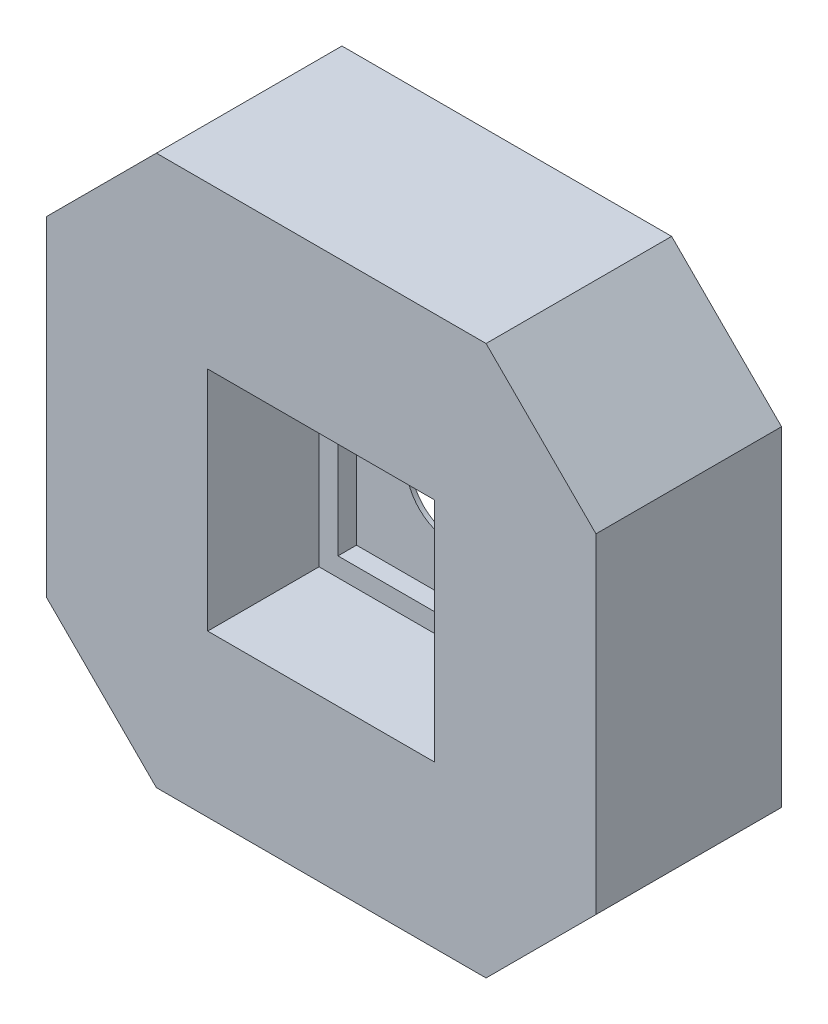
SolidWorks part; units mm, degrees
ref_plane "前视基准面" through (0, 0, 0) normal (0, 0, 1) x (1, 0, 0)
ref_plane "上视基准面" through (0, 0, 0) normal (0, 1, 0) x (1, 0, 0)
ref_plane "右视基准面" through (0, 0, 0) normal (1, 0, 0) x (0, 0, -1)
other "Configuration Table"
sketch "草图2" plane through (0, 0, 0) normal (0, 0, 1) x (1, 0, 0)
  line L0 (-183, 305) -> (-305, 183)
  line L1 (183, -305) -> (-183, -305)
  line L2 (305, -183) -> (305, 183)
  line L3 (183, 305) -> (-183, 305)
  line L4 (-305, -183) -> (-305, 183)
  line L5 (305, -305) -> (-305, 305) construction
  line L6 (305, 305) -> (-305, -305) construction
  line L7 (-183, -305) -> (-305, -183)
  line L8 (305, -183) -> (183, -305)
  line L9 (305, 183) -> (183, 305)
  point P0 (0, 0)
  dimension "D1" = 610
  dimension "D2" = 610
extrude "凸台-拉伸1" add sketch "草图2" along normal blind 206
sketch "草图3" plane through (0, 0, 206) normal (0, 0, 1) x (1, 0, 0)
  line L1 (126, -126) -> (-126, -126)
  line L2 (126, -126) -> (126, 126)
  line L3 (126, 126) -> (-126, 126)
  line L4 (-126, -126) -> (-126, 126)
  line L5 (126, -126) -> (-126, 126) construction
  line L6 (126, 126) -> (-126, -126) construction
  point P0 (0, 0)
  dimension "D1" = 252
extrude "切除-拉伸2" cut sketch "草图3" against normal blind 123.6 contours L4 L3 L2 L1
sketch "草图5" plane through (0, 0, 206) normal (0, 0, 1) x (1, 0, 0)
  line L1 (105, -105) -> (-105, -105)
  line L2 (105, -105) -> (105, 105)
  line L3 (105, 105) -> (-105, 105)
  line L4 (-105, -105) -> (-105, 105)
  line L5 (105, -105) -> (-105, 105) construction
  line L6 (105, 105) -> (-105, -105) construction
  point P0 (0, 0)
  dimension "D1" = 210
extrude "切除-拉伸3" cut sketch "草图5" against normal blind 144.2
shell "抽壳1" thickness 5 removed face at (0, 0, 0)
sketch "草图6" plane through (0, 0, 61.8) normal (0, 0, 1) x (1, 0, 0)
  circle A0 centre (0, 0) radius 50
  dimension "D1" = 100
extrude "切除-拉伸4" cut sketch "草图6" against normal through all
ref_plane "基准面4" through (0, 91.5, 0) normal (0, 1, 0) x (1, 0, 0)
sketch "草图9" plane through (0, 91.5, 0) normal (0, 1, 0) x (1, 0, 0)
  line L0 (131.5096, -82.4) -> (299.4959, -112.0205)
  line L1 (131, -77.4) -> (131, -201) construction
  line L2 (131, -77.4) -> (-131, -77.4) construction
  dimension "D1" = 5
  dimension "D2" = 80
rib "筋1" sketch "草图9" sketch "草图9" thickness 10 extrusion direction parallel to sketch draft on no parameters "D1"=10
mirror "镜向1" about plane through (0, 0, 0) normal (0, 1, 0) of "筋1"
pattern_circular "阵列(圆周)2" count 4 over 360 about axis through (0, 0, 0) along (0, 0, 1) of "镜向1" reverse direction yes
